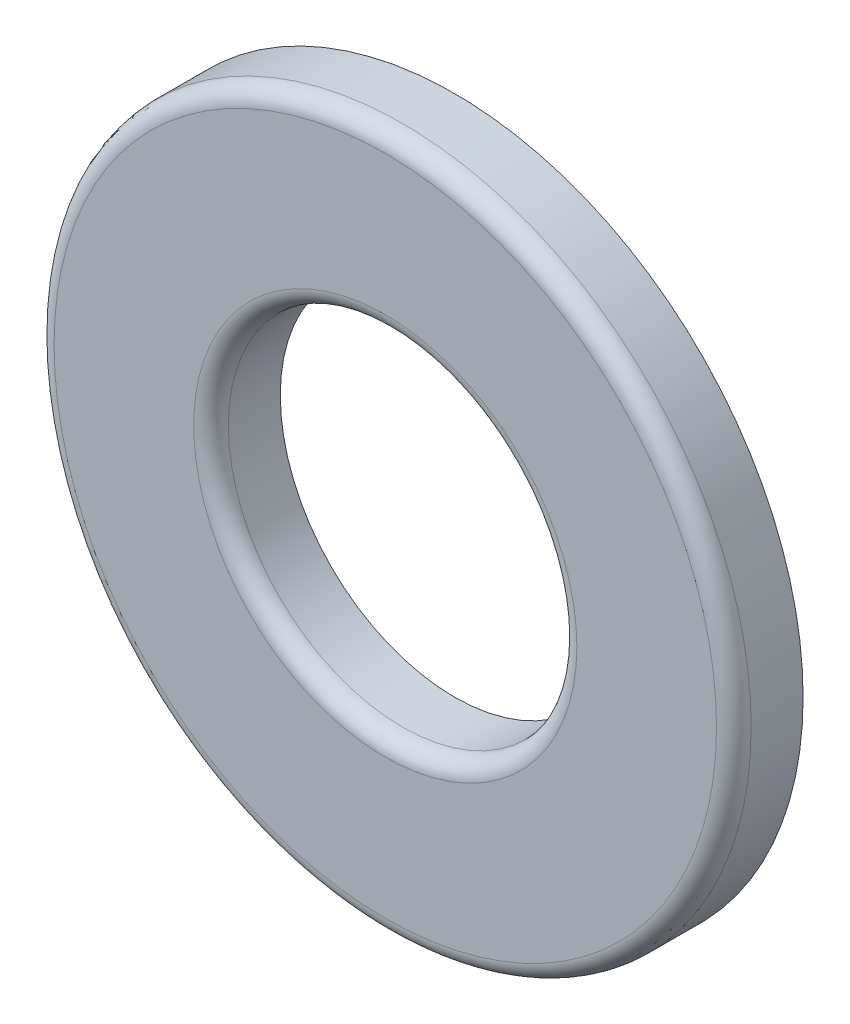
SolidWorks part; units mm, degrees
note: '?' marks a value the reader was unsure of.
other "Imported1" parameters "D1"=0.1968, "TH"=1.0287, "Thickness"=0.7874
ref_plane "Front Plane" through (0, 0, 0) normal (0, 0, 1) x (1, 0, 0)
ref_plane "Top Plane" through (0, 0, 0) normal (0, 1, 0) x (1, 0, 0)
ref_plane "Right Plane" through (0, 0, 0) normal (1, 0, 0) x (0, 0, -1)
sketch "Sketch1" plane through (0, 0, 0) normal (0, 0, 1) x (1, 0, 0)
  line L0 (-3.9624, 0) -> (3.9624, 0) construction
  line L1 (-1.9812, 0) -> (1.9812, 0) construction
  circle A0 centre (0, 0) radius 1.9812 construction
  circle A1 centre (0, 0) radius 3.9624 construction
  point P8 (0, 0)
  point P9 (0, 3.9624)
  point P11 (1.9812, 0)
  dimension "ID" = 3.9624
  dimension "OD" = 7.9248
sketch "Sketch2" plane through (0, 0, 0) normal (1, 0, 0) x (0, 0, -1)
  line L0 (-0.3937, 3.9624) -> (0.3937, 3.9624) construction
  point P2 (0, 3.9624)
sketch "Sketch3" plane through (0, 0, 0) normal (0, 0, 1) x (1, 0, 0)
  circle A0 centre (0, 0) radius 1.9812
  circle A1 centre (0, 0) radius 3.9624
extrude "Boss-Extrude1" add sketch "Sketch3" along normal up to vertex (0.3937 mm away) and the other way up to vertex (0.3937 mm away) up to point (0, 3.9624, 0.3937) other way up to point (0, 3.9624, -0.3937)
fillet "Fillet1" radius 0.1968 2 edges at (3.9624, 0, 0.3937) (1.9812, 0, 0.3937)
ref_axis "Center Axis 1" through (0, 0, 0.1968) along (0, 0, -1)?
equation "\"D1@Fillet1\"=\"Thickness@Sketch2\"/4"
